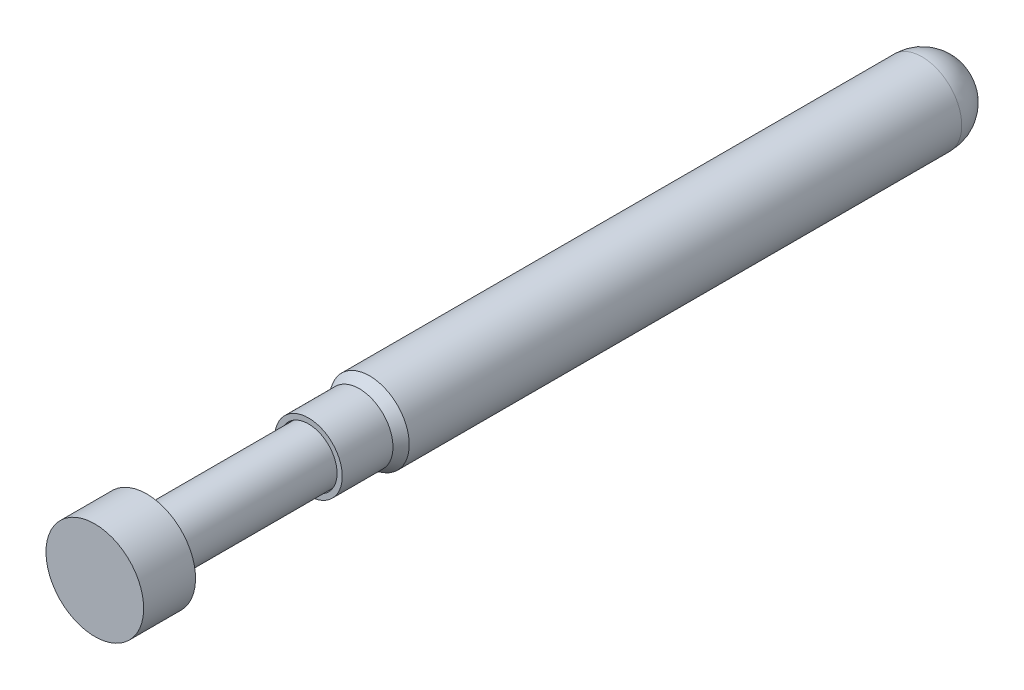
SolidWorks part; units mm, degrees
ref_plane "Front Plane" through (0, 0, 0) normal (0, 0, 1) x (1, 0, 0)
ref_plane "Top Plane" through (0, 0, 0) normal (0, 1, 0) x (1, 0, 0)
ref_plane "Right Plane" through (0, 0, 0) normal (1, 0, 0) x (0, 0, -1)
sketch "Sketch1" plane through (0, 0, 0) normal (1, 0, 0) x (0, 0, -1)
  line L0 (18.034, 0) -> (-18.034, 0) construction
  line L1 (-13.716, 1.1557) -> (-13.716, -1.1557) construction
  line L2 (18.034, -1.651) -> (18.034, 1.651) construction
  line L3 (-18.034, 2.032) -> (-18.034, -2.032) construction
  line L4 (-11.684, 1.1557) -> (-11.684, -1.1557) construction
  line L5 (4.445, 0) -> (4.445, 2.3549) construction
  line L6 (-9.144, 1.651) -> (-9.144, -1.651) construction
  point P0 (-9.144, 0)
  point P3 (-15.494, 0)
  point P4 (0, 0)
  point P8 (18.034, 0)
  point P11 (-18.034, 0)
  point P12 (-11.684, 0)
  point P13 (-13.716, 0)
  point P17 (-11.684, 0)
  point P19 (13.9573, 0)
  point P20 (-5.0673, 0)
  point P25 (-13.716, 0)
  point P26 (-9.144, 0)
  dimension "Overall Length" = 36.068
  dimension "Barrel Diameter" = 3.302
  dimension "Head Diameter" = 4.064
  dimension "Barrel Length" = 27.178
  dimension "Compressed Length" = 29.718
  dimension "Working Stroke Length" = 4.318
  dimension "Maximum Stroke Length" = 6.35
  dimension "Break View" = 19.0246
  dimension "Head Length" = 2.54
  dimension "D1" = 2.3114
sketch "Sketch2" plane through (0, 0, 0) normal (1, 0, 0) x (0, 0, -1)
  line L0 (-9.144, 0) -> (18.034, 0) construction
  line L4 (-6.604, 1.651) -> (16.383, 1.651)
  line L7 (-9.144, 0) -> (-9.144, 1.4034)
  line L8 (-9.144, 1.4034) -> (-7.0329, 1.4034)
  line L9 (-6.604, 1.651) -> (-7.0329, 1.4034)
  line L10 (18.034, 0) -> (-9.144, 0)
  line L11 (16.383, 0) -> (16.383, 1.651) construction
  arc A2 (18.034, 0) -> (16.383, 1.651) centre (16.383, 0) ccw
  point P8 (-6.604, 1.651)
  point P13 (-7.0329, 1.4034)
  point P17 (-7.0329, 1.4034)
  point P21 (-6.604, 1.651)
  dimension "D6" = 3.302
  dimension "D2" = 2.8067
  dimension "D1" = 2.54
  dimension "D3" = 30
revolve "Revolve1" add sketch "Sketch2" angle 360 about L10
sketch "Sketch4" plane through (0, 0, 9.144) normal (0, 0, 1) x (1, 0, 0)
  circle A0 centre (0, 0) radius 1.1887
  dimension "D1" = 2.3774
extrude "Cut-Extrude1" cut sketch "Sketch4" against normal blind 13.335
sketch "Sketch3" plane through (0, 0, 0) normal (1, 0, 0) x (0, 0, -1)
  line L0 (-18.034, 0) -> (-18.034, 2.032)
  line L1 (-18.034, 2.032) -> (-18.034, -2.032) construction
  line L2 (-18.034, 2.032) -> (-15.875, 2.032)
  line L3 (-15.875, 2.032) -> (-15.494, 1.1557)
  line L4 (-15.494, 1.1557) -> (-9.144, 1.1557)
  line L5 (-9.144, 1.1557) -> (-9.144, 0)
  line L6 (-9.144, 1.4034) -> (-9.144, -1.4033) construction
  line L7 (-18.034, 0) -> (-9.144, 0)
  line L8 (18.034, 0) -> (-18.034, 0) construction
  line L9 (0, 0) -> (-9.144, 0) construction
  line L10 (-9.144, 1.1557) -> (-2.794, 1.1557)
  line L11 (-2.794, 1.1557) -> (-2.794, 0)
  line L12 (-2.794, 0) -> (-9.144, 0)
  point P10 (-15.494, 1.1557)
  dimension "D1" = 2.54
  dimension "D5" = 6.35
  dimension "D3" = 2.3114
  dimension "D2" = 2.159
revolve "Revolve2" add sketch "Sketch3" angle 360 about L9 region at (0, 0.7455, 14.1345) region at (0, 0.5778, 5.969)
ref_axis "Center Axis 1" through (0, 0, 6.604) along (0, 0, -1)
ref_plane "Contact Plane 1" through (0, 0, 18.034) normal (0, 0, 1) x (1, 0, 0)
equation "\"D2@Sketch2\"=\"Barrel Diameter@Sketch1\"*0.85"
equation "\"D1@Sketch2\"=\"Head Length@Sketch1\""
equation "\"D6@Sketch2\"=\"Barrel Diameter@Sketch1\""
equation "\"D1@Sketch3\"=\"Head Length@Sketch1\""
equation "\"Break View@Sketch1\"=\"Barrel Length@Sketch1\" * .7"
equation "\"D1@Sketch4\"=\"Barrel Diameter@Sketch1\"*0.72"
equation "\"D1@Cut-Extrude1\"=\"Maximum Stroke Length@Sketch1\"*2.1"
equation "\"D3@Sketch3\"=\"Barrel Diameter@Sketch1\"*0.70"
equation "\"D2@Sketch3\"=\"D1@Sketch3\"*0.85"
equation "\"D5@Sketch3\"=\"Maximum Stroke Length@Sketch1\""
equation "\"D1@Sketch1\"=0.7*\"Barrel Diameter@Sketch1\""
